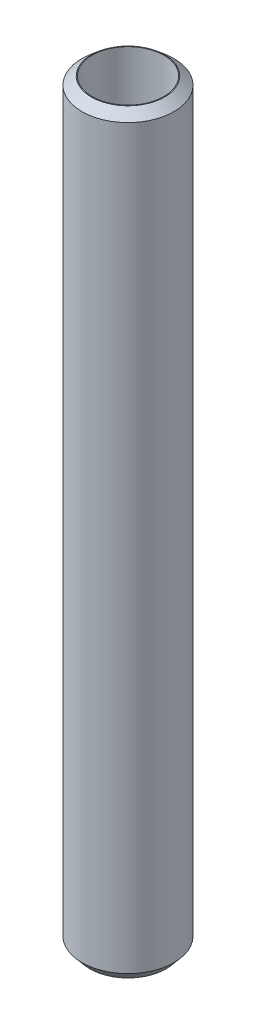
SolidWorks part; units mm, degrees
ref_plane "Front Plane" through (0, 0, 0) normal (0, 0, 1) x (1, 0, 0)
ref_plane "Top Plane" through (0, 0, 0) normal (0, 1, 0) x (1, 0, 0)
ref_plane "Right Plane" through (0, 0, 0) normal (1, 0, 0) x (0, 0, -1)
sketch "Sketch1" plane through (0, 0, 0) normal (0, 1, 0) x (1, 0, 0)
  circle A0 centre (0, 0) radius 30
  dimension "SHAFT_OD" = 60
extrude "Boss-Extrude1" add sketch "Sketch1" along normal blind 491.7726
sketch "Sketch2" plane through (0, 0, 0) normal (0, 1, 0) x (1, 0, 0)
  circle A0 centre (0, 0) radius 23.3751
  dimension "BORE_D" = 46.7501
extrude "Cut-Extrude1" cut sketch "Sketch2" along normal through all
chamfer "Chamfer1" distance 5.1703 angle 49.787 2 edges at (0, 491.7726, 30) (0, 0, 30) first distance on face at (0, 491.7726, 30) first distance on face at (0, 0, 23.3751)
